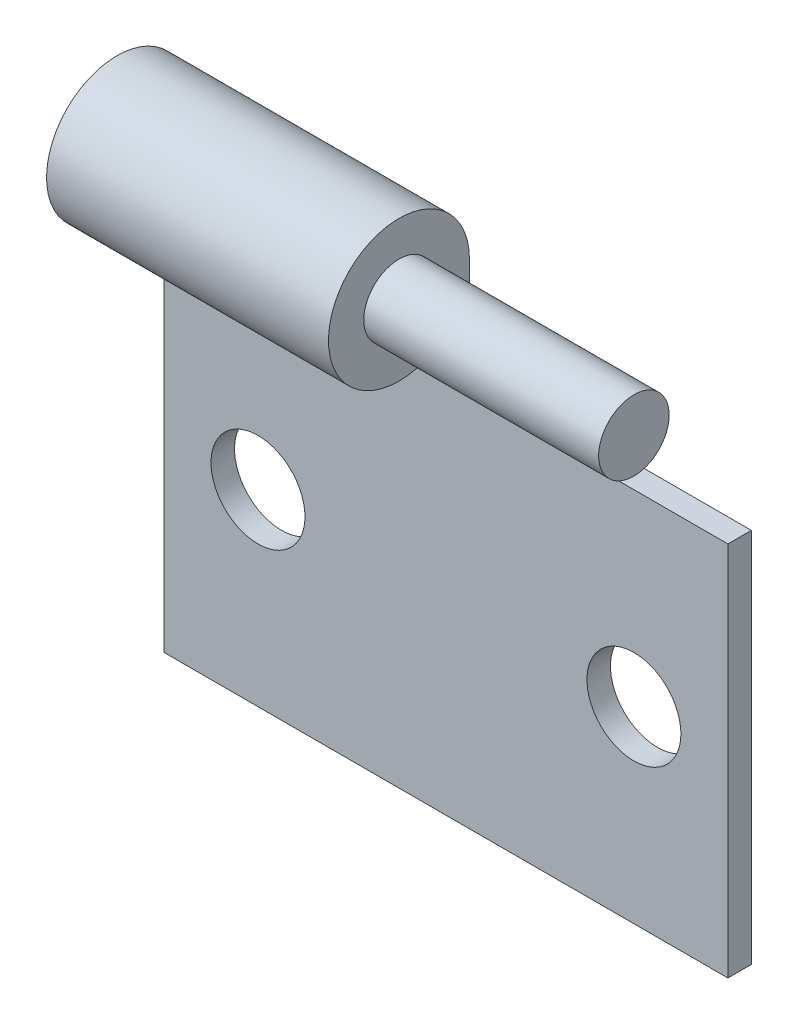
SolidWorks part; units mm, degrees
ref_plane "Front Plane" through (0, 0, 0) normal (0, 0, 1) x (1, 0, 0)
ref_plane "Top Plane" through (0, 0, 0) normal (0, 1, 0) x (1, 0, 0)
ref_plane "Right Plane" through (0, 0, 0) normal (1, 0, 0) x (0, 0, -1)
sketch "Sketch1" plane through (0, 0, 0) normal (0, 0, 1) x (1, 0, 0)
  line L0 (-25.4, 0) -> (25.4, 0) construction
  line L1 (-38.1, -25.4) -> (38.1, -25.4)
  line L2 (-38.1, -25.4) -> (-38.1, 25.4)
  line L3 (-38.1, 25.4) -> (38.1, 25.4)
  line L4 (38.1, -25.4) -> (38.1, 25.4)
  line L5 (-38.1, -25.4) -> (38.1, 25.4) construction
  line L6 (-38.1, 25.4) -> (38.1, -25.4) construction
  circle A0 centre (-25.4, 0) radius 6.35
  circle A1 centre (25.4, 0) radius 6.35
  point P0 (0, 0)
  point P9 (0, 0)
  dimension "D4" = 12.7
  dimension "D1" = 50.8
  dimension "D2" = 76.2
  dimension "D3" = 50.8
extrude "Boss-Extrude1" add sketch "Sketch1" along normal blind 3.175
sketch "Sketch2" plane through (0, 0, 0) normal (1, 0, 0) x (0, 0, -1)
  line L0 (0, -25.4) -> (0, 25.4) construction
  line L1 (-9.525, 38.1) -> (0, 38.1) construction
  line L2 (0, 38.1) -> (0, 25.4)
  line L6 (-3.175, 25.4) -> (-3.175, 31.0005)
  line L7 (-3.175, 25.4) -> (0, 25.4)
  arc A0 (0, 38.1) -> (-3.175, 31.0005) centre (-9.525, 38.1) ccw
  dimension "D1" = 19.05
  dimension "D2" = 12.7
extrude "Boss-Extrude2" add sketch "Sketch2" against normal blind 38.1
fillet "Fillet1" radius 3.175 1 edges at (-19.05, 31.0005, 3.175)
sketch "Sketch3" plane through (0, 0, 0) normal (1, 0, 0) x (0, 0, -1)
  circle A0 centre (-9.525, 38.1) radius 4.7625
  dimension "D1" = 9.525
extrude "Cut-Extrude1" [suppressed] cut sketch "Sketch3" against normal blind 31.75
extrude "Boss-Extrude3" add sketch "Sketch3<2>" along normal blind 31.75
sketch "Sketch3<2>" plane through (0, 0, 0) normal (1, 0, 0) x (0, 0, -1) same geometry as "Sketch3"
